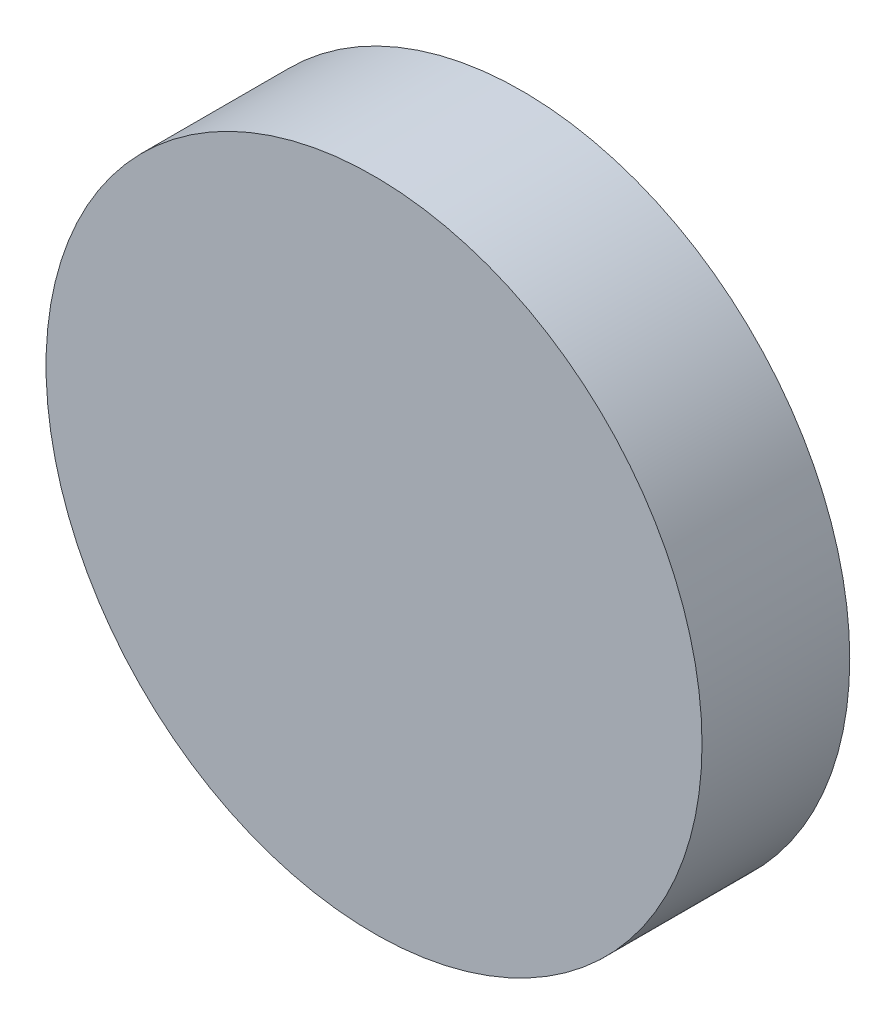
SolidWorks part; units mm, degrees
ref_plane "Front Plane" through (0, 0, 0) normal (0, 0, 1) x (1, 0, 0)
ref_plane "Top Plane" through (0, 0, 0) normal (0, 1, 0) x (1, 0, 0)
ref_plane "Right Plane" through (0, 0, 0) normal (1, 0, 0) x (0, 0, -1)
sketch "Sketch1" plane through (0, 0, -12) normal (0, 0, 1) x (1, 0, 0)
  circle A1 centre (0, 0) radius 4.4404
  dimension "D1" = 8.8807
extrude "Boss-Extrude1" add sketch "Sketch1" along normal blind 2
